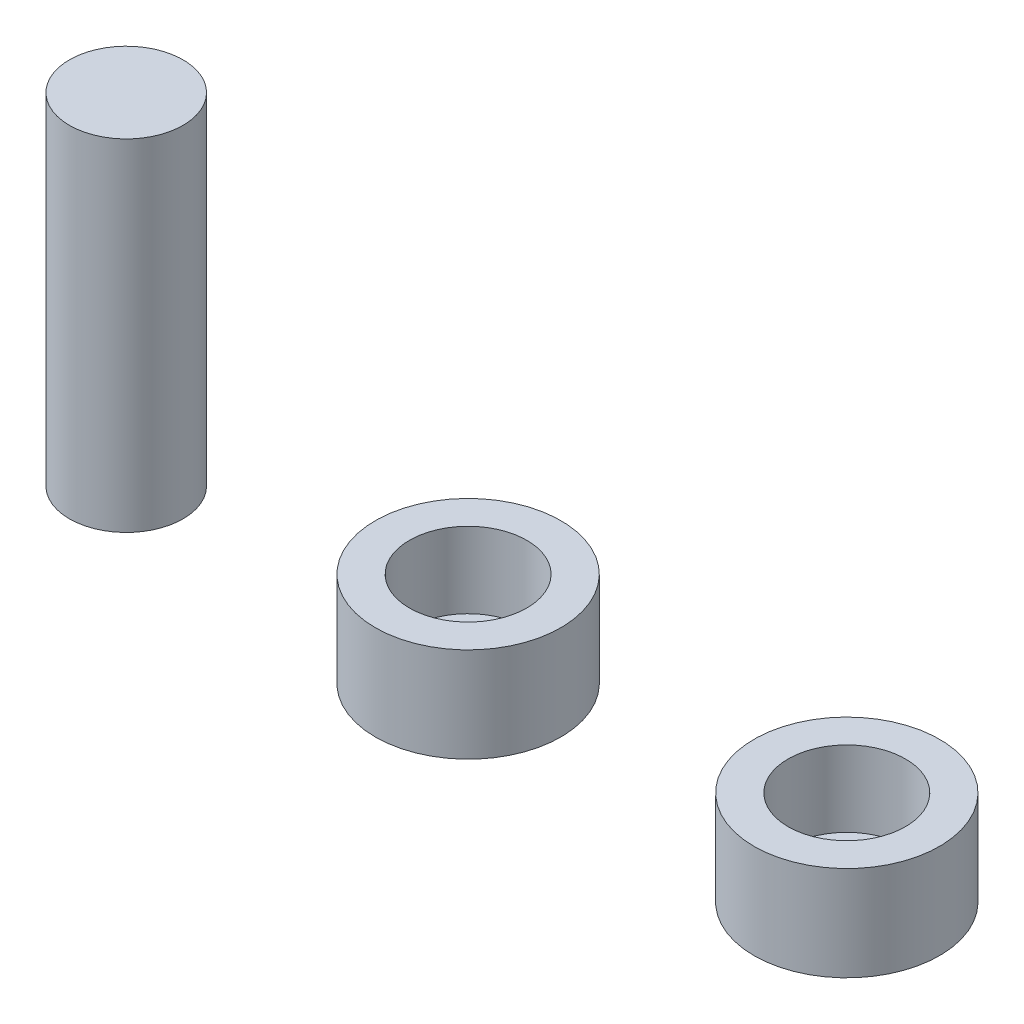
SolidWorks part; units mm, degrees
ref_plane "Front Plane" through (0, 0, 0) normal (0, 0, 1) x (1, 0, 0)
ref_plane "Top Plane" through (0, 0, 0) normal (0, 1, 0) x (1, 0, 0)
ref_plane "Right Plane" through (0, 0, 0) normal (1, 0, 0) x (0, 0, -1)
sketch "Sketch1" plane through (0, 0, 0) normal (0, 1, 0) x (1, 0, 0)
  line L0 (-9.6635, 0) -> (10.2555, 0) construction
  circle A0 centre (0, 0) radius 2.45
  dimension "D1" = 4.9
extrude "Boss-Extrude1" add sketch "Sketch1" along normal blind 2.5
sketch "Sketch2" plane through (0, 0, 0) normal (0, 1, 0) x (1, 0, 0)
  line L0 (-13.1071, 0) -> (16.2343, 0) construction
  circle A0 centre (-9.0273, 0) radius 1.5
  dimension "D1" = 3
extrude "Boss-Extrude2" add sketch "Sketch2" along normal blind 9 separate body contours A0
sketch "Sketch4" plane through (0, 2.5, 0) normal (0, 1, 0) x (1, 0, 0)
  line L0 (-2.5821, 0) -> (3.9052, 0) construction
  circle A0 centre (0, 0) radius 1.55
  dimension "D1" = 3.1
extrude "Cut-Extrude1" cut sketch "Sketch4" against normal blind 2
ref_plane "Plane1" through (5, 0, 0) normal (1, 0, 0) x (0, 0, -1)
mirror "Mirror1" about plane through (5, 0, 0) normal (1, 0, 0) of bodies 104 101
